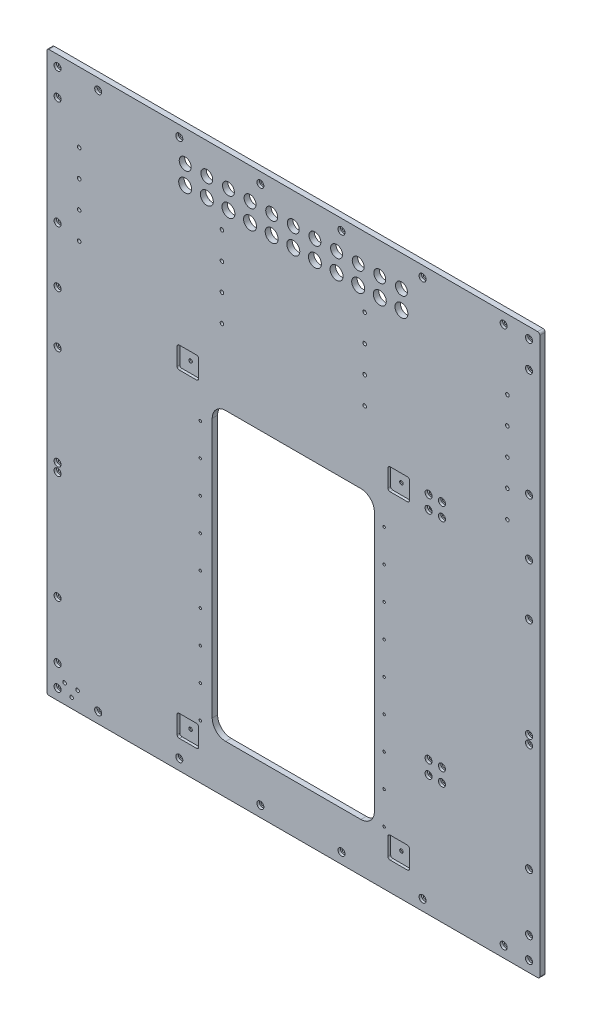
SolidWorks part; units mm, degrees
note: '?' marks a value the reader was unsure of.
ref_plane "Plan de face" through (0, 0, 0) normal (0, 0, 1) x (1, 0, 0)
ref_plane "Plan de dessus" through (0, 0, 0) normal (0, 1, 0) x (1, 0, 0)
ref_plane "Plan de droite" through (0, 0, 0) normal (1, 0, 0) x (0, 0, -1)
sketch "Esquisse1" plane through (0, 0, 0) normal (0, 0, 1) x (1, 0, 0)
  line L1 (-452, -517.5) -> (452, -517.5)
  line L2 (-456, -513.5) -> (-456, 513.5)
  line L3 (-452, 517.5) -> (452, 517.5)
  line L4 (456, -513.5) -> (456, 513.5)
  line L5 (-456, -517.5) -> (456, 517.5) construction
  line L6 (-456, 517.5) -> (456, -517.5) construction
  line L7 (0, 282.5) -> (0, -517.5) construction
  line L8 (-456, 0) -> (456, 0) construction
  arc A0 (-456, 513.5) -> (-452, 517.5) centre (-452, 513.5) cw
  arc A1 (456, 513.5) -> (452, 517.5) centre (452, 513.5) ccw
  arc A2 (452, -517.5) -> (456, -513.5) centre (452, -513.5) ccw
  arc A3 (-456, -513.5) -> (-452, -517.5) centre (-452, -513.5) ccw
  point P0 (0, 0)
  dimension "D3" = 4
  dimension "D4" = 4
  dimension "D5" = 4
  dimension "D6" = 4
  dimension "D1" = 912
  dimension "D2" = 1035
extrude "Boss.-Extru.1" add sketch "Esquisse1" along normal blind 10
sketch "Esquisse2" plane through (0, 0, 10) normal (0, 0, 1) x (1, 0, 0)
  line L0 (-125, -427.5) -> (125, -427.5)
  line L1 (-150, -402.5) -> (-150, 77.5)
  line L2 (150, -402.5) -> (150, 77.5)
  line L3 (-125, 102.5) -> (125, 102.5)
  line L4 (-125, -402.5) -> (125, 77.5) construction
  line L5 (-452, -517.5) -> (452, -517.5) construction
  arc A0 (-125, 102.5) -> (-150, 77.5) centre (-125, 77.5) ccw
  arc A1 (125, 102.5) -> (150, 77.5) centre (125, 77.5) cw
  arc A2 (150, -402.5) -> (125, -427.5) centre (125, -402.5) cw
  arc A3 (-150, -402.5) -> (-125, -427.5) centre (-125, -402.5) ccw
  point P9 (150, 102.5)
  point P12 (150, -427.5)
  dimension "D3" = 300
  dimension "D2" = 25
  dimension "D1" = 530
  dimension "D4" = 90
extrude "Enlèv. mat.-Extru.1" cut sketch "Esquisse2" against normal through all
hole_wizard "Dégagement M61" [suppressed] positions "Esquisse4" profile "Esquisse3" hole size "M6" standard "JIS"
sketch "Esquisse4" plane through (0, 0, 10) normal (0, 0, 1) x (1, 0, 0)
  point P0 (-277.4372, 232)
  point P2 (-247.5898, 232)
  point P4 (-247.5898, 201.8404)
  point P6 (-277.6003, 201.8404)
  point P8 (-262.5, 217)
sketch "Esquisse3" plane through (-277.4372, 232, 10) normal (1, 0, 0) x (0, -1, 0)
  line L0 (0, 0) -> (0, 10)
  line L1 (0, 10) -> (3.3, 10)
  line L2 (3.3, 10) -> (3.3, 0)
  line L5 (3.3, 0) -> (0, 0)
  line L11 (0, -6.35) -> (0, 107.95) construction
  dimension "Diamètre du perçage jusqu'au prochain" = 6.6
  dimension "Profondeur du perçage jusqu'au prochain" = 10
pattern_linear "Répétition linéaire1" [suppressed] count 2 spacing 245
hole_wizard "Chambrage pour vis à tête ronde bombée M61" [suppressed] positions "Esquisse6" profile "Esquisse5" counterbore size "M6" standard "Ansi Metric"
sketch "Esquisse6" plane through (0, 0, 0) normal (0, 0, -1) x (-1, 0, 0)
  point P0 (247.5898, 232)
  point P2 (277.4372, 232)
  point P4 (277.6003, 201.8404)
  point P6 (247.5898, 201.8404)
  point P8 (262.5, 217)
  point P10 (247.5898, -13)
  point P12 (277.4372, -13)
  point P14 (262.5, -28)
sketch "Esquisse5" plane through (-247.5898, 232, 0) normal (1, 0, 0) x (0, 1, 0)
  line L0 (0, 0) -> (0, 10)
  line L1 (0, 10) -> (3.3, 10)
  line L2 (3.3, 4.625) -> (3.3, 10)
  line L3 (3.3, 4.625) -> (3.325, 4.6)
  line L4 (3.325, 4.6) -> (6.5, 4.6)
  line L5 (6.5, 4.6) -> (6.5, 0)
  line L7 (0, 0) -> (6.5, 0)
  line L9 (-3.3, 4.625) -> (-3.325, 4.6) construction
  line L11 (0, -6.35) -> (0, 107.95) construction
  dimension "Diamètre du perçage jusqu'au prochain" = 6.6
  dimension "Profondeur du perçage jusqu'au prochain" = 10
  dimension "Diamètre du chambrage" = 13
  dimension "Profondeur du chambrage" = 4.6
  dimension "Diamètre du fraisage milieu" = 6.65
  dimension "Angle du fraisage milieu" = 90
hole_wizard "Chambrage pour vis à tête ronde bombée M62" [suppressed] positions "Esquisse8" profile "Esquisse7" counterbore size "M6" standard "Ansi Metric"
sketch "Esquisse8" plane through (0, 0, 0) normal (0, 0, -1) x (-1, 0, 0)
  point P0 (247.5898, -43.1596)
  point P2 (277.6003, -43.1596)
sketch "Esquisse7" plane through (-247.5898, -43.1596, 0) normal (1, 0, 0) x (0, 1, 0)
  line L0 (0, 0) -> (0, 10)
  line L1 (0, 10) -> (3.3, 10)
  line L2 (3.3, 4.625) -> (3.3, 10)
  line L3 (3.3, 4.625) -> (3.325, 4.6)
  line L4 (3.325, 4.6) -> (6.5, 4.6)
  line L5 (6.5, 4.6) -> (6.5, 0)
  line L7 (0, 0) -> (6.5, 0)
  line L9 (-3.3, 4.625) -> (-3.325, 4.6) construction
  line L11 (0, -6.35) -> (0, 107.95) construction
  dimension "Diamètre du perçage jusqu'au prochain" = 6.6
  dimension "Profondeur du perçage jusqu'au prochain" = 10
  dimension "Diamètre du chambrage" = 13
  dimension "Profondeur du chambrage" = 4.6
  dimension "Diamètre du fraisage milieu" = 6.65
  dimension "Angle du fraisage milieu" = 90
hole_wizard "Dégagement M62" [suppressed] positions "Esquisse10" profile "Esquisse9" hole size "M6" standard "JIS"
sketch "Esquisse10" plane through (0, 0, 0) normal (0, 0, -1) x (-1, 0, 0)
  point P0 (-209.6182, 209)
  point P2 (-180.0241, 209)
  point P4 (-180.0241, 179.1391)
  point P6 (-209.6182, 179)
  point P8 (-195, 194)
sketch "Esquisse9" plane through (209.6182, 209, 0) normal (1, 0, 0) x (0, 1, 0)
  line L0 (0, 0) -> (0, 10)
  line L1 (0, 10) -> (3.3, 10)
  line L2 (3.3, 10) -> (3.3, 0)
  line L5 (3.3, 0) -> (0, 0)
  line L11 (0, -6.35) -> (0, 107.95) construction
  dimension "Diamètre du perçage jusqu'au prochain" = 6.6
  dimension "Profondeur du perçage jusqu'au prochain" = 10
pattern_linear "Répétition linéaire2" [suppressed] count 2 spacing 390 count 2 spacing 380
hole_wizard "Chambrage pour vis à tête ronde bombée M63" [suppressed] positions "Esquisse14" profile "Esquisse13" counterbore size "M6" standard "Ansi Metric"
sketch "Esquisse14" plane through (0, 0, 10) normal (0, 0, 1) x (1, 0, 0)
  point P0 (-209.9759, 209)
  point P2 (-180.3818, 209)
  point P4 (-180.3818, 179)
  point P6 (-209.9759, 179)
  point P8 (-195, 194)
sketch "Esquisse13" plane through (-209.9759, 209, 10) normal (1, 0, 0) x (0, -1, 0)
  line L0 (0, 0) -> (0, 10)
  line L1 (0, 10) -> (3.3, 10)
  line L2 (3.3, 4.625) -> (3.3, 10)
  line L3 (3.3, 4.625) -> (3.325, 4.6)
  line L4 (3.325, 4.6) -> (6.5, 4.6)
  line L5 (6.5, 4.6) -> (6.5, 0)
  line L7 (0, 0) -> (6.5, 0)
  line L9 (-3.3, 4.625) -> (-3.325, 4.6) construction
  line L11 (0, -6.35) -> (0, 107.95) construction
  dimension "Diamètre du perçage jusqu'au prochain" = 6.6
  dimension "Profondeur du perçage jusqu'au prochain" = 10
  dimension "Diamètre du chambrage" = 13
  dimension "Profondeur du chambrage" = 4.6
  dimension "Diamètre du fraisage milieu" = 6.65
  dimension "Angle du fraisage milieu" = 90
pattern_linear "Répétition linéaire3" [suppressed] count 2 spacing 390 count 2 spacing 380
pattern_linear "Répétition linéaire4" [suppressed] count 2 spacing 27
hole_wizard "Dégagement M63" [suppressed] positions "Esquisse16" profile "Esquisse15" hole size "M6" standard "JIS"
sketch "Esquisse16" plane through (0, 0, 0) normal (0, 0, -1) x (-1, 0, 0)
  point P0 (-195, 109.5)
  point P2 (-209.9493, 94.5)
  point P4 (-209.9493, 124.6707)
  point P6 (-180.2902, 124.6707)
  point P8 (-180.2902, 94.5)
sketch "Esquisse15" plane through (195, 109.5, 0) normal (1, 0, 0) x (0, 1, 0)
  line L0 (0, 0) -> (0, 10)
  line L1 (0, 10) -> (3.3, 10)
  line L2 (3.3, 10) -> (3.3, 0)
  line L5 (3.3, 0) -> (0, 0)
  line L11 (0, -6.35) -> (0, 107.95) construction
  dimension "Diamètre du perçage jusqu'au prochain" = 6.6
  dimension "Profondeur du perçage jusqu'au prochain" = 10
pattern_linear "Répétition linéaire5" [suppressed] count 2 spacing 390 count 2 spacing 555
hole_wizard "Dégagement M41" positions "Esquisse24" profile "Esquisse23" hole size "M4" standard "JIS" end condition through all
sketch "Esquisse24" plane through (0, 0, 10) normal (0, 0, 1) x (1, 0, 0)
  point P0 (-172, -417.5)
sketch "Esquisse23" plane through (-172, -417.5, 10) normal (1, 0, 0) x (0, -1, 0)
  line L0 (0, 0) -> (0, 10)
  line L1 (0, 10) -> (2.25, 10)
  line L2 (2.25, 10) -> (2.25, 0)
  line L5 (2.25, 0) -> (0, 0)
  line L11 (0, -6.35) -> (0, 107.95) construction
  dimension "Diamètre du perçage jusqu'au prochain" = 4.5
  dimension "Profondeur du perçage jusqu'au prochain" = 10
pattern_linear "Répétition linéaire8" count 9 spacing 60 along (0, 1, 0) count 2 spacing 340 along (1, 0, 0) of "Dégagement M41"
hole_wizard "Dégagement M65" positions "Esquisse26" profile "Esquisse25" hole size "M6" standard "JIS" end condition through all
sketch "Esquisse26" plane through (0, 0, 0) normal (0, 0, -1) x (-1, 0, 0)
  point P0 (-436, 497.5)
  point P10 (-436, 448.2864)
  point P12 (-389.1232, 497.5)
  point P18 (-436, -457.5)
  point P20 (-436, -497.5)
  point P26 (-389.1232, -497.5)
  point P32 (436, -457.5)
  point P34 (436, -497.5)
sketch "Esquisse25" plane through (436, 497.5, 0) normal (1, 0, 0) x (0, 1, 0)
  line L0 (0, 0) -> (0, 10)
  line L1 (0, 10) -> (3.3, 10)
  line L2 (3.3, 10) -> (3.3, 0)
  line L5 (3.3, 0) -> (0, 0)
  line L11 (0, -6.35) -> (0, 107.95) construction
  dimension "Diamètre du perçage jusqu'au prochain" = 6.6
  dimension "Profondeur du perçage jusqu'au prochain" = 10
hole_wizard "Chambrage pour vis à tête ronde bombée M66" positions "Esquisse28" profile "Esquisse27" counterbore size "M6" standard "Ansi Metric" end condition through all
sketch "Esquisse28" plane through (0, 0, 10) normal (0, 0, 1) x (1, 0, 0)
  point P0 (436, 497.5)
sketch "Esquisse27" plane through (436, 497.5, 10) normal (1, 0, 0) x (0, -1, 0)
  line L0 (0, 0) -> (0, 10)
  line L1 (0, 10) -> (3.3, 10)
  line L2 (3.3, 4.625) -> (3.3, 10)
  line L3 (3.3, 4.625) -> (3.325, 4.6)
  line L4 (3.325, 4.6) -> (6.5, 4.6)
  line L5 (6.5, 4.6) -> (6.5, 0)
  line L7 (0, 0) -> (6.5, 0)
  line L9 (-3.3, 4.625) -> (-3.325, 4.6) construction
  line L11 (0, -6.35) -> (0, 107.95) construction
  dimension "Diamètre du perçage jusqu'au prochain" = 6.6
  dimension "Profondeur du perçage jusqu'au prochain" = 10
  dimension "Diamètre du chambrage" = 13
  dimension "Profondeur du chambrage" = 4.6
  dimension "Diamètre du fraisage milieu" = 6.65
  dimension "Angle du fraisage milieu" = 90
pattern_linear "Répétition linéaire9" count 2 spacing 872 along (-1, 0, 0) of "Chambrage pour vis à tête ronde bombée M66"
hole_wizard "Chambrage pour vis à tête ronde bombée M67" positions "Esquisse30" profile "Esquisse29" counterbore size "M6" standard "Ansi Metric" end condition through all
sketch "Esquisse30" plane through (0, 0, 10) normal (0, 0, 1) x (1, 0, 0)
  point P0 (389.1232, 497.5)
sketch "Esquisse29" plane through (389.1232, 497.5, 10) normal (1, 0, 0) x (0, -1, 0)
  line L0 (0, 0) -> (0, 10)
  line L1 (0, 10) -> (3.3, 10)
  line L2 (3.3, 4.625) -> (3.3, 10)
  line L3 (3.3, 4.625) -> (3.325, 4.6)
  line L4 (3.325, 4.6) -> (6.5, 4.6)
  line L5 (6.5, 4.6) -> (6.5, 0)
  line L7 (0, 0) -> (6.5, 0)
  line L9 (-3.3, 4.625) -> (-3.325, 4.6) construction
  line L11 (0, -6.35) -> (0, 107.95) construction
  dimension "Diamètre du perçage jusqu'au prochain" = 6.6
  dimension "Profondeur du perçage jusqu'au prochain" = 10
  dimension "Diamètre du chambrage" = 13
  dimension "Profondeur du chambrage" = 4.6
  dimension "Diamètre du fraisage milieu" = 6.65
  dimension "Angle du fraisage milieu" = 90
pattern_linear "Répétition linéaire10" count 6 spacing 150 along (-1, 0, 0) of "Chambrage pour vis à tête ronde bombée M67"
hole_wizard "Chambrage pour vis à tête ronde bombée M68" positions "Esquisse32" profile "Esquisse31" counterbore size "M6" standard "Ansi Metric" end condition through all
sketch "Esquisse32" plane through (0, 0, 10) normal (0, 0, 1) x (1, 0, 0)
  point P0 (436, 448.2864)
sketch "Esquisse31" plane through (436, 448.2864, 10) normal (1, 0, 0) x (0, -1, 0)
  line L0 (0, 0) -> (0, 10)
  line L1 (0, 10) -> (3.3, 10)
  line L2 (3.3, 4.625) -> (3.3, 10)
  line L3 (3.3, 4.625) -> (3.325, 4.6)
  line L4 (3.325, 4.6) -> (6.5, 4.6)
  line L5 (6.5, 4.6) -> (6.5, 0)
  line L7 (0, 0) -> (6.5, 0)
  line L9 (-3.3, 4.625) -> (-3.325, 4.6) construction
  line L11 (0, -6.35) -> (0, 107.95) construction
  dimension "Diamètre du perçage jusqu'au prochain" = 6.6
  dimension "Profondeur du perçage jusqu'au prochain" = 10
  dimension "Diamètre du chambrage" = 13
  dimension "Profondeur du chambrage" = 4.6
  dimension "Diamètre du fraisage milieu" = 6.65
  dimension "Angle du fraisage milieu" = 90
pattern_linear "Répétition linéaire11" count 5 spacing 200 along (0, -1, 0) count 2 spacing 872 along (-1, 0, 0) of "Chambrage pour vis à tête ronde bombée M68"
hole_wizard "Chambrage pour vis à tête ronde bombée M69" positions "Esquisse34" profile "Esquisse33" counterbore size "M6" standard "Ansi Metric" end condition through all
sketch "Esquisse34" plane through (0, 0, 10) normal (0, 0, 1) x (1, 0, 0)
  point P0 (436, -457.5)
  point P2 (436, -497.5)
sketch "Esquisse33" plane through (436, -457.5, 10) normal (1, 0, 0) x (0, -1, 0)
  line L0 (0, 0) -> (0, 10)
  line L1 (0, 10) -> (3.3, 10)
  line L2 (3.3, 4.625) -> (3.3, 10)
  line L3 (3.3, 4.625) -> (3.325, 4.6)
  line L4 (3.325, 4.6) -> (6.5, 4.6)
  line L5 (6.5, 4.6) -> (6.5, 0)
  line L7 (0, 0) -> (6.5, 0)
  line L9 (-3.3, 4.625) -> (-3.325, 4.6) construction
  line L11 (0, -6.35) -> (0, 107.95) construction
  dimension "Diamètre du perçage jusqu'au prochain" = 6.6
  dimension "Profondeur du perçage jusqu'au prochain" = 10
  dimension "Diamètre du chambrage" = 13
  dimension "Profondeur du chambrage" = 4.6
  dimension "Diamètre du fraisage milieu" = 6.65
  dimension "Angle du fraisage milieu" = 90
pattern_linear "Répétition linéaire13" count 2 spacing 872 along (-1, 0, 0) of "Chambrage pour vis à tête ronde bombée M69"
hole_wizard "Chambrage pour vis à tête ronde bombée M610" positions "Esquisse36" profile "Esquisse35" counterbore size "M6" standard "Ansi Metric" end condition through all
sketch "Esquisse36" plane through (0, 0, 10) normal (0, 0, 1) x (1, 0, 0)
  point P0 (389.1232, -497.5)
sketch "Esquisse35" plane through (389.1232, -497.5, 10) normal (1, 0, 0) x (0, -1, 0)
  line L0 (0, 0) -> (0, 10)
  line L1 (0, 10) -> (3.3, 10)
  line L2 (3.3, 4.625) -> (3.3, 10)
  line L3 (3.3, 4.625) -> (3.325, 4.6)
  line L4 (3.325, 4.6) -> (6.5, 4.6)
  line L5 (6.5, 4.6) -> (6.5, 0)
  line L7 (0, 0) -> (6.5, 0)
  line L9 (-3.3, 4.625) -> (-3.325, 4.6) construction
  line L11 (0, -6.35) -> (0, 107.95) construction
  dimension "Diamètre du perçage jusqu'au prochain" = 6.6
  dimension "Profondeur du perçage jusqu'au prochain" = 10
  dimension "Diamètre du chambrage" = 13
  dimension "Profondeur du chambrage" = 4.6
  dimension "Diamètre du fraisage milieu" = 6.65
  dimension "Angle du fraisage milieu" = 90
pattern_linear "Répétition linéaire14" count 6 spacing 150 along (-1, 0, 0) of "Chambrage pour vis à tête ronde bombée M610"
sketch "Esquisse41" plane through (0, 0, 10) normal (0, 0, 1) x (1, 0, 0)
  line L0 (452, 517.5) -> (-452, 517.5) construction
  line L1 (-456, 513.5) -> (-456, -513.5) construction
  circle A0 centre (-436, 144.5) radius 1.5
  circle A1 centre (-436, -136.5) radius 1.5
  dimension "D1" = 3
  dimension "D2" = 373
  dimension "D3" = 20
  dimension "D4" = 2
extrude "Enlèv. mat.-Extru.2" cut sketch "Esquisse41" against normal through all
ref_point "Point1"
ref_axis "Axe1" through (0, 517.5, 5) along (0, 1, 0)?
ref_plane "Plan1" through (0, 0, 0) normal (1, 0, 0) x (0, 1, 0)
mirror "Symétrie1" about plane through (0, 0, 0) normal (1, 0, 0) of "Enlèv. mat.-Extru.2"
hole_wizard "Chambrage pour vis à tête ronde bombée M611" positions "Esquisse43" profile "Esquisse44" counterbore size "M6" standard "Ansi Metric" end condition through all
sketch "Esquisse43" plane through (0, 0, 10) normal (0, 0, 1) x (1, 0, 0)
  point P0 (-436, 144.5)
  point P4 (-436, -136.5)
  point P7 (436, -136.5)
  point P10 (436, 144.5)
sketch "Esquisse44" plane through (-436, 144.5, 10) normal (1, 0, 0) x (0, -1, 0)
  line L0 (0, 0) -> (0, 10)
  line L1 (0, 10) -> (3.3, 10)
  line L2 (3.3, 4.625) -> (3.3, 10)
  line L3 (3.3, 4.625) -> (3.325, 4.6)
  line L4 (3.325, 4.6) -> (6.5, 4.6)
  line L5 (6.5, 4.6) -> (6.5, 0)
  line L7 (0, 0) -> (6.5, 0)
  line L9 (-3.3, 4.625) -> (-3.325, 4.6) construction
  line L11 (0, -6.35) -> (0, 107.95) construction
  dimension "Diamètre du perçage jusqu'au prochain" = 6.6
  dimension "Profondeur du perçage jusqu'au prochain" = 10
  dimension "Diamètre du chambrage" = 13
  dimension "Profondeur du chambrage" = 4.6
  dimension "Diamètre du fraisage milieu" = 6.65
  dimension "Angle du fraisage milieu" = 90
hole_wizard "Dégagement M67" positions "Esquisse46" profile "Esquisse45" hole size "M6" standard "JIS" end condition through all
sketch "Esquisse46" plane through (0, 0, 0) normal (0, 0, -1) x (-1, 0, 0)
  point P0 (-396.0014, 188.3978)
sketch "Esquisse45" plane through (396.0014, 188.3978, 0) normal (1, 0, 0) x (0, 1, 0)
  line L0 (0, 0) -> (0, 10)
  line L1 (0, 10) -> (3.3, 10)
  line L2 (3.3, 10) -> (3.3, 0)
  line L5 (3.3, 0) -> (0, 0)
  line L11 (0, -6.35) -> (0, 107.95) construction
  dimension "Diamètre du perçage jusqu'au prochain" = 6.6
  dimension "Profondeur du perçage jusqu'au prochain" = 10
pattern_linear "Répétition linéaire15" count 4 spacing 264 along (-1, 0, 0) count 5 spacing 50 along (0, 1, 0) skipping (1, 0), (2, 0), (3, 0) of "Dégagement M67"
hole_wizard "Dégagement M68" positions "Esquisse48" profile "Esquisse47" hole size "M6" standard "JIS" end condition through all
sketch "Esquisse48" plane through (0, 0, 0) normal (0, 0, -1) x (-1, 0, 0)
  point P9 (-195, 144.5)
sketch "Esquisse47" plane through (195, 144.5, 0) normal (1, 0, 0) x (0, 1, 0)
  line L0 (0, 0) -> (0, 10)
  line L1 (0, 10) -> (3.3, 10)
  line L2 (3.3, 10) -> (3.3, 0)
  line L5 (3.3, 0) -> (0, 0)
  line L11 (0, -6.35) -> (0, 107.95) construction
  dimension "Diamètre du perçage jusqu'au prochain" = 6.6
  dimension "Profondeur du perçage jusqu'au prochain" = 10
hole_wizard "Chambrage pour vis à tête ronde bombée M41" positions "Esquisse50" profile "Esquisse49" counterbore size "M4" standard "Ansi Metric" end condition through all
sketch "Esquisse50" plane through (0, 0, 10) normal (0, 0, 1) x (1, 0, 0)
  point P4 (195, 144.5)
sketch "Esquisse49" plane through (195, 144.5, 10) normal (1, 0, 0) x (0, -1, 0)
  line L0 (0, 0) -> (0, 10)
  line L1 (0, 10) -> (2.25, 10)
  line L2 (2.25, 3.125) -> (2.25, 10)
  line L3 (2.25, 3.125) -> (2.275, 3.1)
  line L4 (2.275, 3.1) -> (4.5, 3.1)
  line L5 (4.5, 3.1) -> (4.5, 0)
  line L7 (0, 0) -> (4.5, 0)
  line L9 (-2.25, 3.125) -> (-2.275, 3.1) construction
  line L11 (0, -6.35) -> (0, 107.95) construction
  dimension "Diamètre du perçage jusqu'au prochain" = 4.5
  dimension "Profondeur du perçage jusqu'au prochain" = 10
  dimension "Diamètre du chambrage" = 9
  dimension "Profondeur du chambrage" = 3.1
  dimension "Diamètre du fraisage milieu" = 4.55
  dimension "Angle du fraisage milieu" = 90
pattern_linear "Répétition linéaire16" count 2 spacing 390 along (-1, 0, 0) count 2 spacing 590 along (0, -1, 0) of "Chambrage pour vis à tête ronde bombée M41"
sketch "Esquisse51" plane through (0, 0, 0) normal (0, 0, 1) x (1, 0, 0)
  spline S0 degree 1 poles (246.5761, 163.5395) (278.5761, 163.5395) knots 0 0 1 1
  spline S1 degree 2 poles (278.5761, 163.5395) (282.2329, 163.1964) (282.5761, 159.5395) knots 0 0 0 1 1 1
  spline S2 degree 2 poles (282.5761, 159.5395) (282.5761, 144.5111) (282.5761, 127.5395) knots 0 0 0 1 1 1
  spline S3 degree 2 poles (282.5761, 127.5395) (282.2329, 123.8826) (278.5761, 123.5395) knots 0 0 0 1 1 1
  spline S4 degree 1 poles (278.5761, 123.5395) (246.5761, 123.5395) knots 0 0 1 1
  spline S5 degree 2 poles (246.5761, 123.5395) (242.9192, 123.8826) (242.5761, 127.5395) knots 0 0 0 1 1 1
  spline S6 degree 1 poles (242.5761, 127.5395) (242.5761, 159.5395) knots 0 0 1 1
  spline S7 degree 2 poles (242.5761, 159.5395) (242.9192, 163.1964) (246.5761, 163.5395) knots 0 0 0 1 1 1
sketch "Esquisse52" plane through (0, 0, 10) normal (0, 0, -1) x (-1, 0, 0)
  spline S0 degree 1 poles (-211, -425.5) (-179, -425.5) knots 0 0 1 1
  spline S1 degree 2 poles (-179, -425.5) (-175.3431, -425.8431) (-175, -429.5) knots 0 0 0 1 1 1
  spline S2 degree 1 poles (-175, -429.5) (-175, -461.5) knots 0 0 1 1
  spline S3 degree 2 poles (-175, -461.5) (-175.3431, -465.1569) (-179, -465.5) knots 0 0 0 1 1 1
  spline S4 degree 1 poles (-179, -465.5) (-211, -465.5) knots 0 0 1 1
  spline S5 degree 2 poles (-211, -465.5) (-214.6569, -465.1569) (-215, -461.5) knots 0 0 0 1 1 1
  spline S6 degree 1 poles (-215, -461.5) (-215, -429.5) knots 0 0 1 1
  spline S7 degree 2 poles (-215, -429.5) (-214.6569, -425.8431) (-211, -425.5) knots 0 0 0 1 1 1
extrude "Enlèv. mat.-Extru.6" cut sketch "Esquisse52" along normal blind 5
pattern_linear "Répétition linéaire18" count 2 spacing 590 along (0, 1, 0) count 2 spacing 390 along (-1, 0, 0) of "Enlèv. mat.-Extru.6"
extrude "Enlèv. mat.-Extru.9" cut sketch "Esquisse51" along normal blind 5
pattern_linear "Répétition linéaire20" count 2 spacing 425 along (0, 1, 0) of "Enlèv. mat.-Extru.9"
hole_wizard "M6 Clearance Hole1" positions "Sketch4" profile "Sketch3" hole size "M6" standard "ANSI Metric" end condition through all
sketch "Sketch4" plane through (0, 0, 5) normal (0, 0, -1) x (-1, 0, 0)
  point P0 (-274.9505, 155.9139)
  point P3 (-250.2017, 155.9139)
  point P6 (-250.2017, 131.1651)
  point P9 (-274.9505, 131.1651)
sketch "Sketch3" plane through (274.9505, 155.9139, 5) normal (1, 0, 0) x (0, 1, 0)
  line L0 (0, 0) -> (0, 5)
  line L1 (0, 5) -> (3.3, 5)
  line L2 (3.3, 5) -> (3.3, 0)
  line L5 (3.3, 0) -> (0, 0)
  line L11 (0, -6.35) -> (0, 107.95) construction
  dimension "Thru Hole Dia." = 6.6
  dimension "Thru Hole Depth" = 5
hole_wizard "CBORE for M6 Pan Head Machine Screw2" positions "Sketch8" profile "Sketch7" counterbore size "M6" standard "ANSI Metric" end condition through all
sketch "Sketch8" plane through (0, 0, 10) normal (0, 0, 1) x (1, 0, 0)
  point P0 (274.9505, 155.9139)
  point P3 (250.2017, 155.9139)
  point P6 (250.2017, 131.1651)
  point P9 (274.9505, 131.1651)
sketch "Sketch7" plane through (274.9505, 155.9139, 10) normal (1, 0, 0) x (0, -1, 0)
  line L0 (0, 0) -> (0, 10)
  line L1 (0, 10) -> (3.3, 10)
  line L2 (3.3, 4.625) -> (3.3, 10)
  line L3 (3.3, 4.625) -> (3.325, 4.6)
  line L4 (3.325, 4.6) -> (6.5, 4.6)
  line L5 (6.5, 4.6) -> (6.5, 0)
  line L7 (0, 0) -> (6.5, 0)
  line L9 (-3.3, 4.625) -> (-3.325, 4.6) construction
  line L11 (0, -6.35) -> (0, 107.95) construction
  dimension "Thru Hole Dia." = 6.6
  dimension "Thru Hole Depth" = 10
  dimension "C'Bore Dia." = 13
  dimension "C'Bore Depth" = 4.6
  dimension "Mid C'Sink Dia." = 6.65
  dimension "Mid C'Sink Angle" = 90
pattern_linear "LPattern2" count 2 spacing 425 along (0, -1, 0) of "CBORE for M6 Pan Head Machine Screw2"
hole_wizard "CBORE for M6 Pan Head Machine Screw3" positions "Sketch10" profile "Sketch9" counterbore size "M6" standard "ANSI Metric" end condition through all
sketch "Sketch10" plane through (0, 0, 0) normal (0, 0, -1) x (-1, 0, 0)
  point P0 (-195, 144.5)
  point P3 (195, 144.5)
  point P6 (195, -445.5)
  point P9 (-195, -445.5)
sketch "Sketch9" plane through (195, 144.5, 0) normal (1, 0, 0) x (0, 1, 0)
  line L0 (0, 0) -> (0, 10)
  line L1 (0, 10) -> (3.3, 10)
  line L2 (3.3, 4.625) -> (3.3, 10)
  line L3 (3.3, 4.625) -> (3.325, 4.6)
  line L4 (3.325, 4.6) -> (6.5, 4.6)
  line L5 (6.5, 4.6) -> (6.5, 0)
  line L7 (0, 0) -> (6.5, 0)
  line L9 (-3.3, 4.625) -> (-3.325, 4.6) construction
  line L11 (0, -6.35) -> (0, 107.95) construction
  dimension "Thru Hole Dia." = 6.6
  dimension "Thru Hole Depth" = 10
  dimension "C'Bore Dia." = 13
  dimension "C'Bore Depth" = 4.6
  dimension "Mid C'Sink Dia." = 6.65
  dimension "Mid C'Sink Angle" = 90
sketch "Sketch11" plane through (0, 0, 0) normal (0, 0, -1) x (-1, 0, 0)
  line L0 (-416, 408.3978) -> (416, 408.3978) construction
  line L1 (-416, 408.3978) -> (-416, 477.5) construction
  line L2 (416, 408.3978) -> (416, 477.5) construction
  line L3 (-416, 477.5) -> (416, 477.5) construction
  line L4 (-456, -513.5) -> (-456, 513.5) construction
  line L5 (456, 513.5) -> (456, -513.5) construction
  line L6 (-452, 517.5) -> (452, 517.5) construction
  line L7 (-416, 442.9489) -> (416, 442.9489) construction
  line L8 (0, 477.5) -> (0, 442.9489) construction
  line L9 (0, 442.9489) -> (0, 408.3978) construction
  circle A0 centre (131.9986, 388.3978) radius 3.3 construction
  circle A1 centre (0, 460.2245) radius 3
  circle A2 centre (0, 425.6734) radius 3
  dimension "D5" = 6
  dimension "D6" = 6
  dimension "D1" = 40
  dimension "D2" = 40
  dimension "D3" = 40
  dimension "D4" = 20
extrude "Cut-Extrude1" cut sketch "Sketch11" against normal blind 10
hole_wizard "M20 Clearance Hole1" positions "Sketch15" profile "Sketch14" hole size "M20" standard "ANSI Metric" end condition through all
sketch "Sketch15" plane through (0, 0, 0) normal (0, 0, -1) x (-1, 0, 0)
  point P0 (0, 460.2245)
sketch "Sketch14" plane through (0, 460.2245, 0) normal (1, 0, 0) x (0, 1, 0)
  line L0 (0, 0) -> (0, 10)
  line L1 (0, 10) -> (11, 10)
  line L2 (11, 10) -> (11, 0)
  line L5 (11, 0) -> (0, 0)
  line L11 (0, -6.35) -> (0, 107.95) construction
  dimension "Thru Hole Dia." = 22
  dimension "Thru Hole Depth" = 10
hole_wizard "M22 Clearance Hole1" positions "Sketch19" profile "Sketch18" hole size "M22" standard "ANSI Metric" end condition through all
sketch "Sketch19" plane through (0, 0, 0) normal (0, 0, -1) x (-1, 0, 0)
  point P0 (0, 425.6734)
sketch "Sketch18" plane through (0, 425.6734, 0) normal (1, 0, 0) x (0, 1, 0)
  line L0 (0, 0) -> (0, 10)
  line L1 (0, 10) -> (12, 10)
  line L2 (12, 10) -> (12, 0)
  line L5 (12, 0) -> (0, 0)
  line L11 (0, -6.35) -> (0, 107.95) construction
  dimension "Thru Hole Dia." = 24
  dimension "Thru Hole Depth" = 10
pattern_linear "LPattern3" count 6 spacing 40 along (1, 0, 0) of "M20 Clearance Hole1", "M22 Clearance Hole1"
pattern_linear "LPattern4" count 6 spacing 40 along (-1, 0, 0) of "M20 Clearance Hole1", "M22 Clearance Hole1"
hole_wizard "M6 Clearance Hole2" positions "Sketch21" profile "Sketch20" hole size "M6" standard "ANSI Metric" end condition through all
sketch "Sketch21" plane through (0, 0, 10) normal (0, 0, 1) x (1, 0, 0)
  point P0 (-410, -499.5)
  point P2 (-399, -482.6544)
  point P4 (-423, -482.6544)
sketch "Sketch20" plane through (-410, -499.5, 10) normal (1, 0, 0) x (0, -1, 0)
  line L0 (0, 0) -> (0, 10)
  line L1 (0, 10) -> (3.3, 10)
  line L2 (3.3, 10) -> (3.3, 0)
  line L5 (3.3, 0) -> (0, 0)
  line L11 (0, -6.35) -> (0, 107.95) construction
  dimension "Thru Hole Dia." = 6.6
  dimension "Thru Hole Depth" = 10
